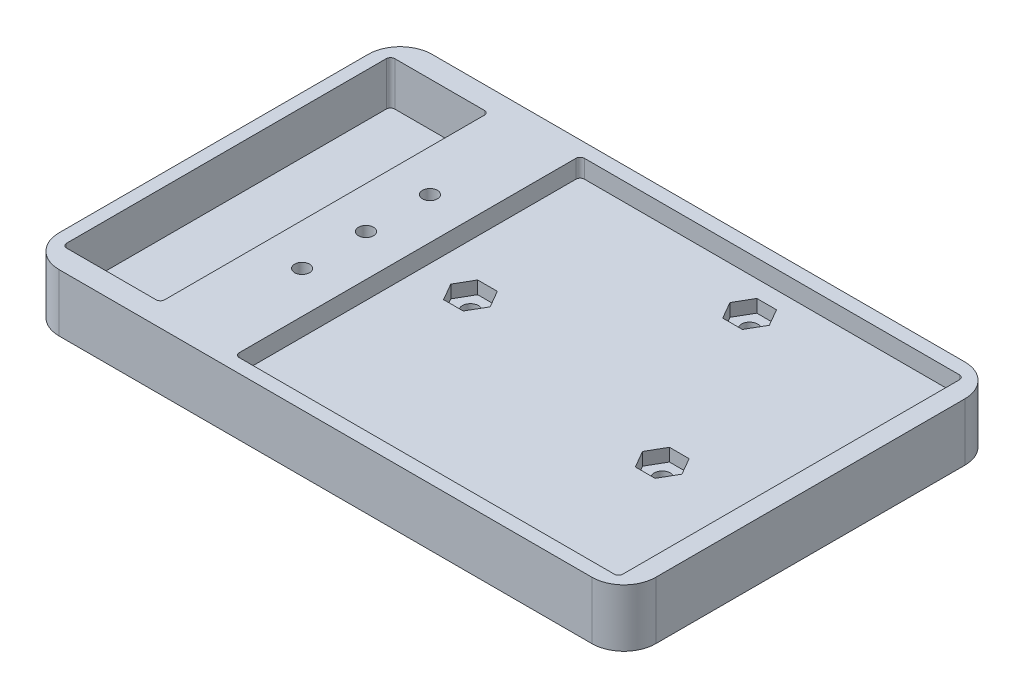
SolidWorks part; units mm, degrees
ref_plane "Front Plane" through (0, 0, 0) normal (0, 0, 1) x (1, 0, 0)
ref_plane "Top Plane" through (0, 0, 0) normal (0, 1, 0) x (1, 0, 0)
ref_plane "Right Plane" through (0, 0, 0) normal (1, 0, 0) x (0, 0, -1)
sketch "Sketch1" plane through (0, 0, 0) normal (0, 1, 0) x (1, 0, 0)
  line L1 (0, 0) -> (140, 0)
  line L2 (0, 0) -> (0, 87.5)
  line L3 (0, 87.5) -> (140, 87.5)
  line L4 (140, 0) -> (140, 87.5)
  dimension "D1" = 87.5
  dimension "D2" = 140
extrude "Boss-Extrude1" add sketch "Sketch1" along normal blind 13.5
sketch "Sketch2" plane through (0, 13.5, 0) normal (0, 1, 0) x (1, 0, 0)
  line L5 (140, 43.75) -> (135.5, 43.75) construction
  line L7 (45.5, 84.25) -> (135.5, 84.25)
  line L9 (45.5, 84.25) -> (45.5, 3.25)
  line L10 (45.5, 3.25) -> (135.5, 3.25)
  line L11 (135.5, 84.25) -> (135.5, 3.25)
  line L12 (140, 0) -> (140, 87.5) construction
  line L13 (90.5, 84.25) -> (90.5, 87.5) construction
  line L14 (140, 87.5) -> (0, 87.5) construction
  line L15 (90.5, 3.25) -> (90.5, 0) construction
  line L16 (0, 0) -> (140, 0) construction
  dimension "D3" = 81
  dimension "D1" = 4.5
  dimension "D2" = 90
extrude "Cut-Extrude1" cut sketch "Sketch2" against normal blind 4.25
sketch "Sketch5" plane through (0, 13.5, 0) normal (0, 1, 0) x (1, 0, 0)
  line L0 (0, 87.5) -> (0, 0) construction
  line L1 (3, 5.25) -> (26, 5.25)
  line L2 (3, 5.25) -> (3, 82.25)
  line L3 (3, 82.25) -> (26, 82.25)
  line L4 (26, 5.25) -> (26, 82.25)
  line L5 (14.5, 82.25) -> (14.5, 87.5) construction
  line L6 (140, 87.5) -> (0, 87.5) construction
  line L7 (14.5, 5.25) -> (14.5, 0) construction
  line L8 (0, 0) -> (140, 0) construction
  dimension "D1" = 23
  dimension "D2" = 77
  dimension "D3" = 3
extrude "Cut-Extrude2" cut sketch "Sketch5" against normal blind 10.25
sketch "Sketch11" plane through (0, 9.25, 0) normal (0, 1, 0) x (1, 0, 0)
  line L0 (90.5, 84.25) -> (90.5, 3.25) construction
  line L1 (135.5, 84.25) -> (45.5, 84.25) construction
  line L2 (45.5, 3.25) -> (135.5, 3.25) construction
  line L3 (45.5, 43.75) -> (135.5, 43.75) construction
  line L4 (45.5, 84.25) -> (45.5, 3.25) construction
  line L5 (135.5, 3.25) -> (135.5, 84.25) construction
  line L7 (90.5, 43.75) -> (56.75, 43.75) construction
  line L8 (90.5, 43.75) -> (90.5, 47.25) construction
  line L9 (90.5, 47.25) -> (56.75, 47.25) construction
  line L10 (56.75, 43.75) -> (56.75, 47.25) construction
  line L15 (90.5, 43.75) -> (113.25, 43.75) construction
  line L16 (90.5, 43.75) -> (90.5, 35.75) construction
  line L17 (90.5, 35.75) -> (113.25, 35.75) construction
  line L18 (113.25, 43.75) -> (113.25, 35.75) construction
  line L19 (90.5, 43.75) -> (93.25, 43.75) construction
  line L20 (90.5, 43.75) -> (90.5, 76.25) construction
  line L21 (90.5, 76.25) -> (93.25, 76.25) construction
  line L22 (93.25, 43.75) -> (93.25, 76.25) construction
  dimension "D1" = 3.5
  dimension "D2" = 33.75
  dimension "D3" = 32.5
  dimension "D4" = 2.75
  dimension "D5" = 8
  dimension "D6" = 22.75
hole_wizard "#6 Clearance Hole1" positions "Sketch17" profile "Sketch18" hole size "#6" standard "ANSI Inch" end condition through all
sketch "Sketch17" plane through (0, 9.25, 0) normal (0, 1, 0) x (1, 0, 0)
  point P0 (56.75, 47.25)
  point P3 (93.25, 76.25)
  point P6 (113.25, 35.75)
sketch "Sketch18" plane through (56.75, 9.25, -47.25) normal (1, 0, 0) x (0, 0, 1)
  line L0 (0, 0) -> (0, 9.25)
  line L1 (0, 9.25) -> (1.8986, 9.25)
  line L2 (1.8986, 9.25) -> (1.8986, 0)
  line L5 (1.8986, 0) -> (0, 0)
  line L11 (0, -6.35) -> (0, 107.95) construction
  dimension "Thru Hole Dia." = 3.7973
  dimension "Thru Hole Depth" = 9.25
sketch "Sketch19" plane through (0, 9.25, 0) normal (0, 1, 0) x (1, 0, 0)
  line L0 (135.5, 84.25) -> (45.5, 84.25) construction
  line L1 (59.0594, 51.25) -> (54.4406, 51.25)
  line L2 (54.4406, 51.25) -> (52.1312, 47.25)
  line L3 (52.1312, 47.25) -> (54.4406, 43.25)
  line L4 (54.4406, 43.25) -> (59.0594, 43.25)
  line L5 (59.0594, 43.25) -> (61.3688, 47.25)
  line L6 (61.3688, 47.25) -> (59.0594, 51.25)
  line L7 (97.8688, 76.25) -> (95.5594, 80.25)
  line L8 (95.5594, 80.25) -> (90.9406, 80.25)
  line L9 (90.9406, 80.25) -> (88.6312, 76.25)
  line L10 (88.6312, 76.25) -> (90.9406, 72.25)
  line L11 (90.9406, 72.25) -> (95.5594, 72.25)
  line L12 (95.5594, 72.25) -> (97.8688, 76.25)
  line L13 (117.8688, 35.75) -> (115.5594, 39.75)
  line L14 (115.5594, 39.75) -> (110.9406, 39.75)
  line L15 (110.9406, 39.75) -> (108.6312, 35.75)
  line L16 (108.6312, 35.75) -> (110.9406, 31.75)
  line L17 (110.9406, 31.75) -> (115.5594, 31.75)
  line L18 (115.5594, 31.75) -> (117.8688, 35.75)
  line L19 (135.5, 84.25) -> (45.5, 84.25) construction
  circle A0 centre (56.75, 47.25) radius 4 construction
  circle A1 centre (93.25, 76.25) radius 4 construction
  circle A2 centre (113.25, 35.75) radius 4 construction
  dimension "D1" = 8
extrude "Cut-Extrude4" cut sketch "Sketch19" against normal blind 3
fillet "Fillet1" radius 7.5 4 edges at (0, 6.75, 0) (0, 6.75, -87.5) (140, 6.75, -87.5) (140, 6.75, 0)
sketch "Sketch15" plane through (0, 13.5, 0) normal (0, 1, 0) x (1, 0, 0)
  line L0 (26, 43.75) -> (45.5, 43.75) construction
  line L9 (26, 5.25) -> (26, 82.25) construction
  line L10 (45.5, 3.25) -> (45.5, 84.25) construction
  line L12 (35.75, 43.75) -> (35.75, 58.75) construction
  line L14 (35.75, 43.75) -> (35.75, 28.75) construction
  line L15 (132.5, 87.5) -> (7.5, 87.5) construction
  line L17 (7.5, 0) -> (132.5, 0) construction
  line L26 (70, 87.5) -> (70, 0) construction
  circle A4 centre (35.75, 43.75) radius 1.75
  circle A5 centre (35.75, 58.75) radius 1.75
  circle A6 centre (35.75, 28.75) radius 1.75
  dimension "D2" = 3.5
  dimension "D1" = 15
extrude "Cut-Extrude3" cut sketch "Sketch15" against normal blind 10
fillet "Fillet2" radius 1 8 edges at (3, 8.375, -5.25) (26, 8.375, -5.25) (26, 8.375, -82.25) (3, 8.375, -82.25) (135.5, 11.375, -3.25) (45.5, 11.375, -3.25) (135.5, 11.375, -84.25) (45.5, 11.375, -84.25)
